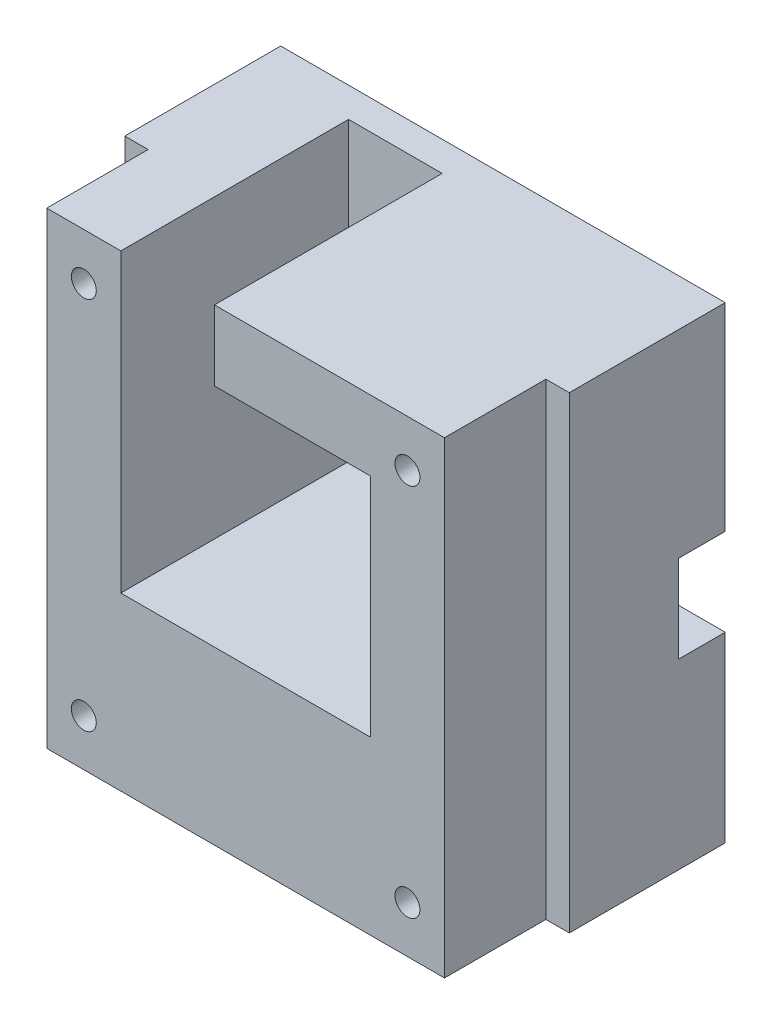
SolidWorks part; units mm, degrees
ref_plane "Front Plane" through (0, 0, 0) normal (0, 0, 1) x (1, 0, 0)
ref_plane "Top Plane" through (0, 0, 0) normal (0, 1, 0) x (1, 0, 0)
ref_plane "Right Plane" through (0, 0, 0) normal (1, 0, 0) x (0, 0, -1)
sketch "Sketch1" plane through (0, 0, 0) normal (0, 0, 1) x (1, 0, 0)
  line L1 (0, 0) -> (28.5, 0)
  line L2 (0, 0) -> (0, 30)
  line L3 (0, 30) -> (28.5, 30)
  line L4 (28.5, 0) -> (28.5, 30)
  dimension "D1" = 28.5
  dimension "D2" = 30
extrude "Boss-Extrude1" add sketch "Sketch1" along normal blind 16.5
sketch "Sketch2" plane through (0, 0, 16.5) normal (0, 0, 1) x (1, 0, 0)
  line L0 (0, 30) -> (0, 0) construction
  line L1 (12.25, 30) -> (12.25, 25.5)
  line L2 (12.25, 25.5) -> (22.25, 25.5)
  line L4 (6.25, 28.4669) -> (6.25, 11)
  line L6 (22.25, 25.5) -> (22.25, 11)
  line L7 (6.25, 28.4669) -> (6.25, 30)
  line L8 (28.5, 30) -> (0, 30) construction
  line L9 (6.25, 30) -> (12.25, 30)
  line L10 (6.25, 11) -> (22.25, 11)
  dimension "D1" = 16
  dimension "D2" = 14.5
  dimension "D3" = 6.25
  dimension "D4" = 6
  dimension "D5" = 4.5
extrude "Cut-Extrude1" cut sketch "Sketch2" against normal blind 14.6
sketch "Sketch3" plane through (0, 0, 1.9) normal (0, 0, 1) x (1, 0, 0)
  line L0 (6.25, 11) -> (22.25, 11) construction
  line L2 (22.25, 11) -> (22.25, 25.5) construction
  circle A0 centre (18.75, 14.5) radius 2.8
  dimension "D2" = 3.5
  dimension "D3" = 5.6
  dimension "D1" = 3.5
extrude "Cut-Extrude2" cut sketch "Sketch3" against normal through all
sketch "Sketch4" plane through (0, 0, 0) normal (0, 0, -1) x (-1, 0, 0)
  line L0 (-18.75, 17.3) -> (-28.5, 17.3)
  line L6 (-28.5, 0) -> (-28.5, 30) construction
  line L7 (-28.5, 17.3) -> (-28.5, 11.7)
  line L8 (-28.5, 11.7) -> (-18.75, 11.7)
  circle A2 centre (-18.75, 14.5) radius 2.8 construction
  arc A3 (-18.75, 11.7) -> (-18.75, 17.3) centre (-18.75, 14.5) cw
extrude "Cut-Extrude3" cut sketch "Sketch4" against normal blind 3
sketch "Sketch5" plane through (0, 0, 0) normal (0, 0, 1) x (1, 0, 0)
  line L0 (28.5, 30) -> (12.25, 30) construction
  line L1 (28.5, 0) -> (28.5, 30) construction
  line L2 (0, 15) -> (28.5, 15) construction
  line L3 (0, 30) -> (0, 0) construction
  line L4 (14.25, 0) -> (14.25, 30) construction
  line L5 (0, 0) -> (28.5, 0) construction
  line L8 (6.25, 30) -> (0, 30) construction
  circle A0 centre (24.625, 27) radius 0.8
  circle A1 centre (24.625, 3) radius 0.8
  circle A2 centre (3.875, 3) radius 0.8
  circle A3 centre (3.875, 27) radius 0.8
  point P14 (14.25, 15)
  point P24 (14.25, 15)
  dimension "D1" = 1.6
  dimension "D4" = 3
  dimension "D6" = 3
  dimension "D2" = 3
  dimension "D3" = 3.875
  dimension "D5" = 3.875
sketch "Sketch7" plane through (0, 0, 16.5) normal (0, 0, 1) x (1, 0, 0)
  line L0 (0, 0) -> (28.5, 0) construction
  line L1 (0, 30) -> (1.5, 30)
  line L2 (0, 30) -> (0, 0)
  line L3 (0, 0) -> (1.5, 0)
  line L4 (1.5, 30) -> (1.5, 0)
  line L6 (28.5, 30) -> (27, 30)
  line L7 (28.5, 30) -> (28.5, 0)
  line L8 (28.5, 0) -> (27, 0)
  line L9 (27, 30) -> (27, 0)
  dimension "D1" = 1.5
  dimension "D2" = 1.5
extrude "Cut-Extrude5" cut sketch "Sketch7" against normal blind 6.5
extrude "Cut-Extrude6" cut sketch "Sketch5" against normal blind 6.5 from surface starting at face at (13.85, 19.3, 16.5)
sketch "Sketch6" plane through (0, 0, 16.5) normal (0, 0, 1) x (1, 0, 0)
  line L0 (22.25, 25.5) -> (6.25, 11) construction
  line L1 (22.25, 11) -> (6.25, 25.5) construction
  line L2 (6.25, 30) -> (6.25, 11) construction
  circle A1 centre (14.25, 18.25) radius 2.8553
  point P9 (14.25, 18.25)
